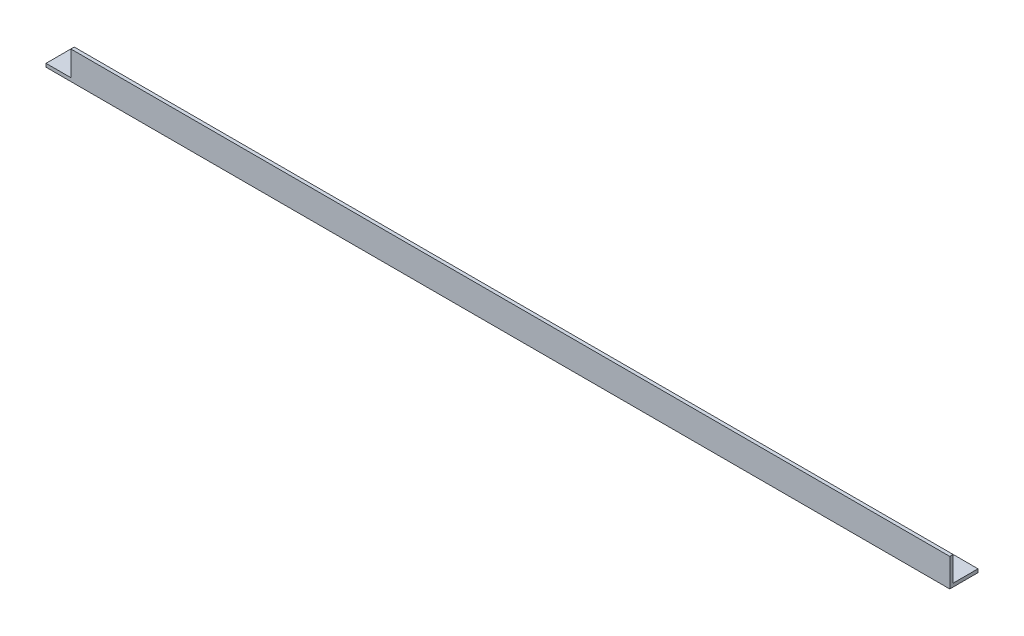
SolidWorks part; units mm, degrees
ref_plane "Спереди" through (0, 0, 0) normal (0, 0, 1) x (1, 0, 0)
ref_plane "Сверху" through (0, 0, 0) normal (0, 1, 0) x (1, 0, 0)
ref_plane "Справа" through (0, 0, 0) normal (1, 0, 0) x (0, 0, -1)
sketch "Эскиз1" plane through (0, 0, 0) normal (1, 0, 0) x (0, 0, -1)
  line L0 (0, 0) -> (25, 0)
  line L1 (0, 0) -> (0, 25)
extrude "Вытянуть-Тонкостенный1" add sketch "Эскиз1" along normal blind 800 thin thin type one direction wall 3
sketch "Эскиз2" plane through (0, 0, 0) normal (0, 0, 1) x (1, 0, 0)
  line L1 (0, 25) -> (22, 25)
  line L2 (0, 25) -> (0, 3)
  line L3 (0, 3) -> (22, 3)
  line L4 (22, 25) -> (22, 3)
extrude "Вырез-Вытянуть1" cut sketch "Эскиз2" against normal through all
